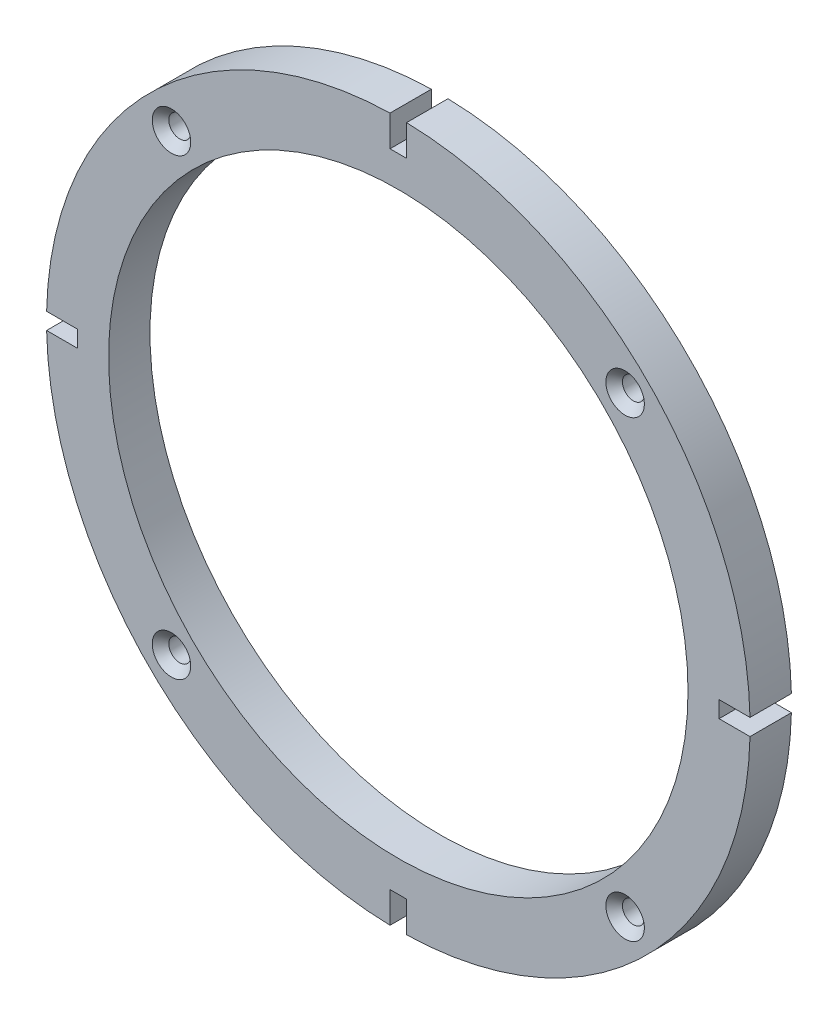
SolidWorks part; units mm, degrees
material "Stop 1060"
ref_plane "Płaszczyzna przednia" through (0, 0, 0) normal (0, 0, 1) x (1, 0, 0)
ref_plane "Płaszczyzna górna" through (0, 0, 0) normal (0, 1, 0) x (1, 0, 0)
ref_plane "Płaszczyzna prawa" through (0, 0, 0) normal (1, 0, 0) x (0, 0, -1)
sketch "Sketch1" plane through (0, 0, 0) normal (0, 0, 1) x (1, 0, 0)
  line L0 (84.9765, -2) -> (77.4996, -2)
  line L1 (-2, 77.4996) -> (2, 77.4996)
  line L2 (-2, 77.4996) -> (-2, 84.9765)
  line L4 (2, 84.9765) -> (2, 77.4996)
  line L5 (77.4996, 2) -> (84.9765, 2)
  line L6 (77.4996, 2) -> (77.4996, -2)
  line L7 (-2, -84.9765) -> (-2, -77.4996)
  line L8 (2, -77.4996) -> (2, -84.9765)
  line L9 (2, -77.4996) -> (-2, -77.4996)
  line L10 (-84.9765, 2) -> (-77.4996, 2)
  line L11 (-77.4996, -2) -> (-84.9765, -2)
  line L12 (-77.4996, -2) -> (-77.4996, 2)
  circle A0 centre (0, 0) radius 70
  arc A1 (-2, 84.9765) -> (-84.9765, 2) centre (0, 0) ccw
  arc A2 (-84.9765, -2) -> (-2, -84.9765) centre (0, 0) ccw
  arc A3 (2, -84.9765) -> (84.9765, -2) centre (0, 0) ccw
  arc A4 (84.9765, 2) -> (2, 84.9765) centre (0, 0) ccw
  point P6 (-2, 77.4996)
  point P7 (2, 77.4996)
  point P24 (0, 0)
  dimension "D1" = 170
  dimension "D2" = 140
  dimension "D3" = 77.4996
  dimension "D4" = 2
  dimension "D5" = 4
  dimension "D6" = 4
extrude "Boss-Extrude1" add sketch "Sketch1" along normal blind 10 contours A0 | A1 L10 L12 L11 A2 L7 L9 L8 A3 L0 L6 L5 A4 L4 L1 L2 region at (0, 0, 0)
sketch "Sketch2" plane through (0, 0, 0) normal (0, 0, -1) x (-1, 0, 0)
  line L0 (0, 0) -> (-73.6832, 73.6832) construction
  line L1 (0, 0) -> (0, 118.1493) construction
  circle A0 centre (-54.8008, 54.8008) radius 2.65
  arc A1 (-2, 84.9765) -> (-84.9765, 2) centre (0, 0) ccw construction
  circle A2 centre (54.8008, 54.8008) radius 2.65
  circle A3 centre (54.8008, -54.8008) radius 2.65
  circle A4 centre (-54.8008, -54.8008) radius 2.65
  point P18 (0, 0)
  dimension "D3" = 5.3
  dimension "D1" = 77.5
  dimension "D2" = 45
  dimension "D4" = 4
extrude "Wytnij-wyciągnięcie1" cut sketch "Sketch2" against normal blind 10
sketch "Szkic1" plane through (0, 0, 0) normal (0, 0, -1) x (-1, 0, 0)
  circle A0 centre (-54.8008, 54.8008) radius 5
  dimension "D1" = 10
extrude "Wytnij-wyciągnięcie2" cut sketch "Szkic1" against normal blind 2 contours A0
pattern_circular "Szyk kołowy1" count 4 over 360 about axis through (0, 0, 10) along (0, 0, -1) of "Wytnij-wyciągnięcie2"
chamfer "Sfazowanie1" distance 2 4 edges at (52.1508, -54.8008, 10) (52.1508, 54.8008, 10) (-57.4508, 54.8008, 10) (-57.4508, -54.8008, 10)
